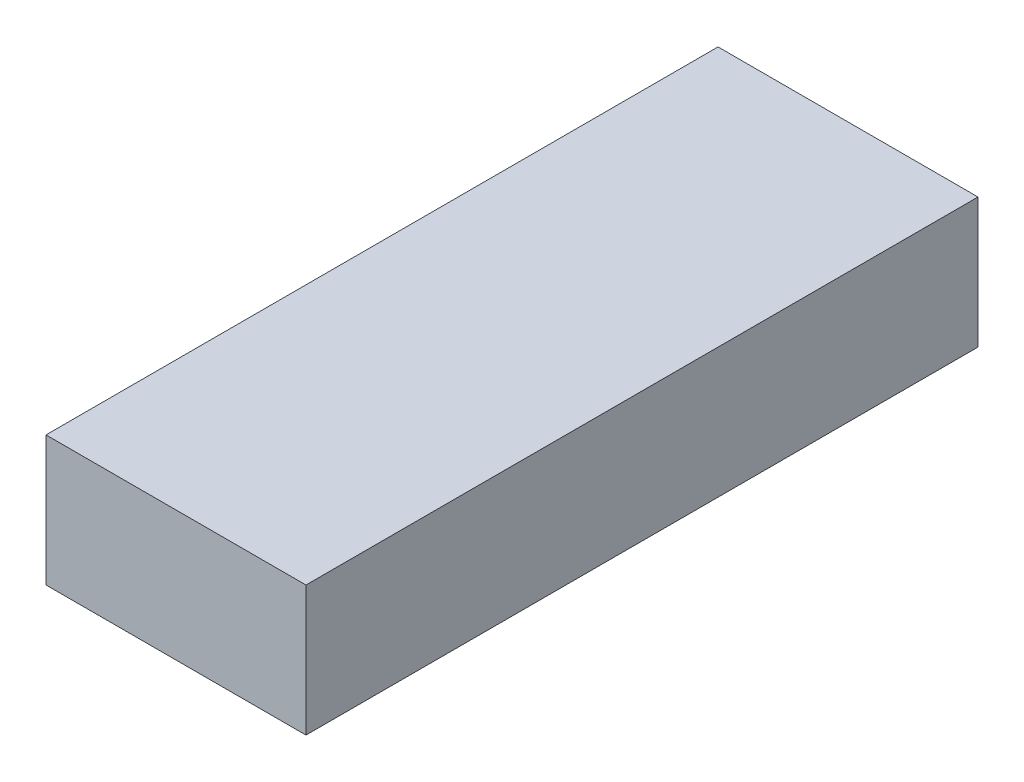
SolidWorks part; units mm, degrees
material "КУ-1"
ref_plane "Спереди" through (0, 0, 0) normal (0, 0, 1) x (1, 0, 0)
ref_plane "Сверху" through (0, 0, 0) normal (0, 1, 0) x (1, 0, 0)
ref_plane "Справа" through (0, 0, 0) normal (1, 0, 0) x (0, 0, -1)
sketch "Эскиз1" plane through (0, 0, 0) normal (0, 0, 1) x (1, 0, 0)
  line L0 (10, 5) -> (-10, -5) construction
  line L1 (-10, 5) -> (10, 5)
  line L2 (-10, 5) -> (-10, -5)
  line L3 (-10, -5) -> (10, -5)
  line L4 (10, 5) -> (10, -5)
  line L5 (-10, 5) -> (10, -5) construction
  dimension "D1" = 10
  dimension "D2" = 20
extrude "Вытянуть1" add sketch "Эскиз1" along normal blind 51.7
sketch "Эскиз2" plane through (0, 5, 0) normal (0, 1, 0) x (-1, 0, 0)
  line L0 (-10, 51.7) -> (10, 0) construction
  line L1 (-10, 0) -> (10, 51.7) construction
  point P8 (0, 25.85)
ref_axis "Ось1" through (0, 5, 25.85) along (0, 1, 0)
